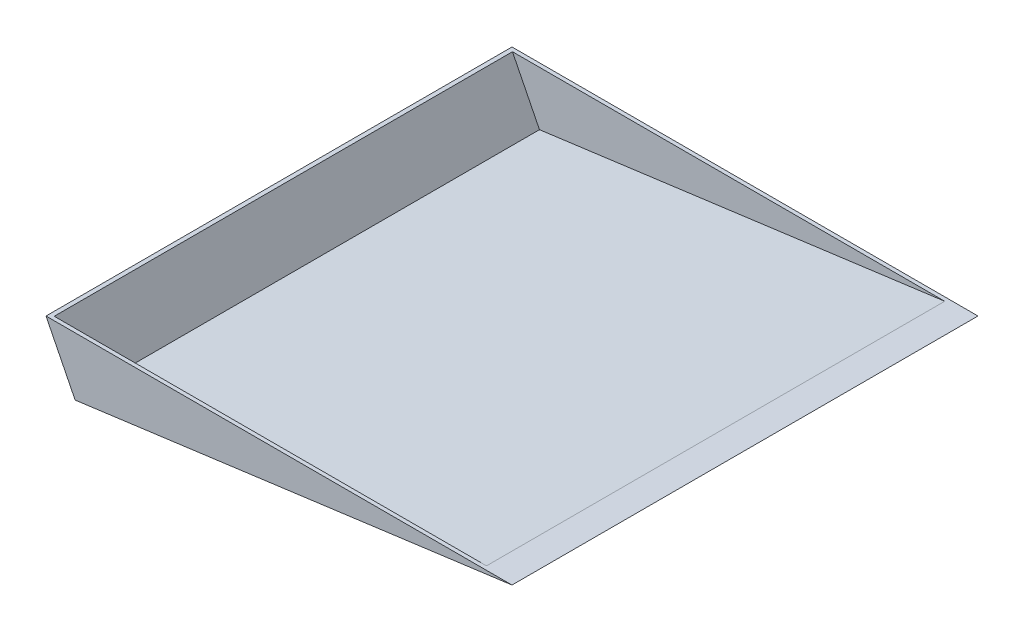
SolidWorks part; units mm, degrees
ref_plane "Front Plane" through (0, 0, 0) normal (0, 0, 1) x (1, 0, 0)
ref_plane "Top Plane" through (0, 0, 0) normal (0, 1, 0) x (1, 0, 0)
ref_plane "Right Plane" through (0, 0, 0) normal (1, 0, 0) x (0, 0, -1)
sketch3d "3DSketch1"
  line L2 (574.7508, 1402.4171, 1756.2546) -> (612.8508, 1326.2171, 1756.2546)
  line L3 (612.8508, 1326.2171, 1756.2546) -> (1184.3508, 1402.4171, 1756.2546)
  line L4 (1184.3508, 1402.4171, 1756.2546) -> (574.7508, 1402.4171, 1756.2546)
extrude "Boss-Extrude1" add sketch "3DSketch1" along a picked direction on the side of the normal blind 609.6 contours L2 L3 L4
shell "Shell1" thickness 5.08 removed face at (1031.9508, 1402.4171, 1603.8546)
